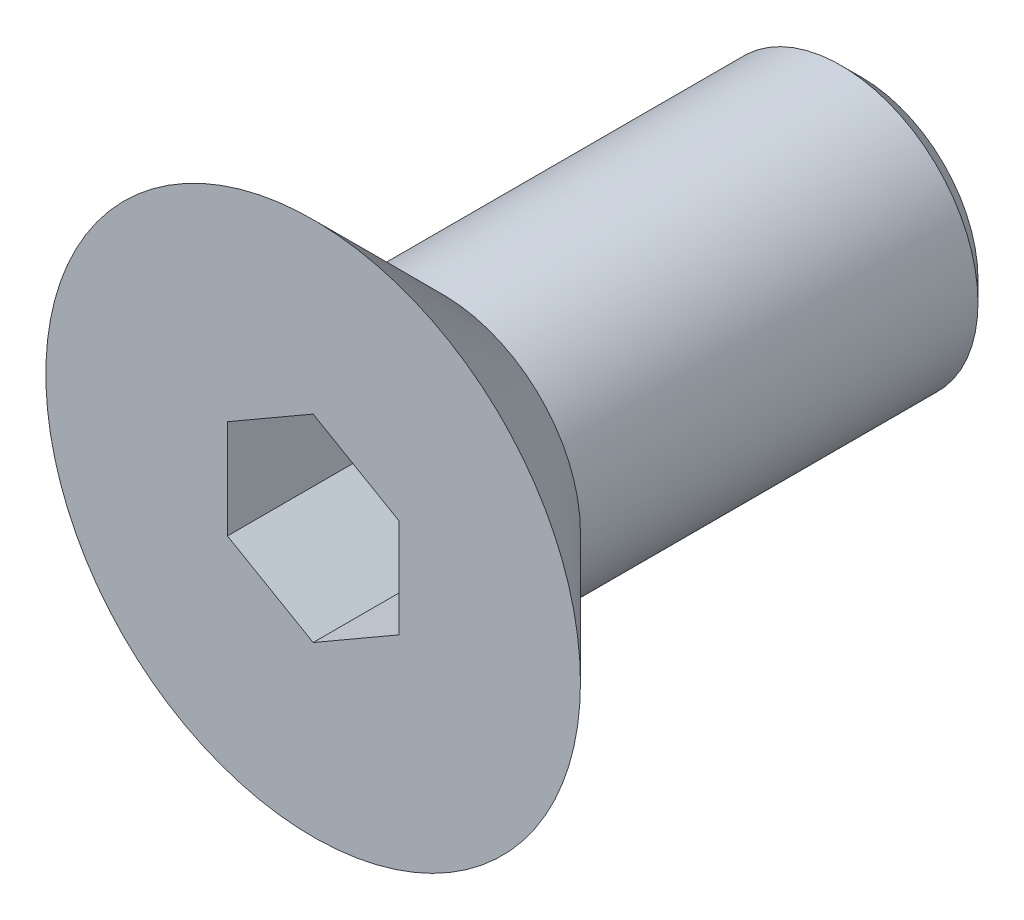
SolidWorks part; units mm, degrees
ref_plane "Front Plane" through (0, 0, 0) normal (0, 0, 1) x (1, 0, 0)
ref_plane "Top Plane" through (0, 0, 0) normal (0, 1, 0) x (1, 0, 0)
ref_plane "Right Plane" through (0, 0, 0) normal (1, 0, 0) x (0, 0, -1)
sketch "Sketch1" plane through (0, 0, 0) normal (0, 0, 1) x (1, 0, 0)
  circle A0 centre (0, 0) radius 4
  dimension "D1" = 8
extrude "Boss-Extrude1" add sketch "Sketch1" along normal blind 2.3
sketch "Sketch2" plane through (0, 0, 0) normal (0, 0, -1) x (-1, 0, 0)
  circle A0 centre (0, 0) radius 2
  dimension "D1" = 4
extrude "Boss-Extrude2" add sketch "Sketch2" along normal blind 5.7
chamfer "Chamfer1" distance 0.3 angle 45 1 edges at (-2, 0, -5.7)
sketch "Sketch3" plane through (0, 0, 2.3) normal (0, 0, 1) x (1, 0, 0)
  line L1 (0, 1.4434) -> (-1.25, 0.7217)
  line L2 (-1.25, 0.7217) -> (-1.25, -0.7217)
  line L3 (-1.25, -0.7217) -> (0, -1.4434)
  line L4 (0, -1.4434) -> (1.25, -0.7217)
  line L5 (1.25, -0.7217) -> (1.25, 0.7217)
  line L6 (1.25, 0.7217) -> (0, 1.4434)
  circle A0 centre (0, 0) radius 1.25 construction
  dimension "D1" = 2.5
extrude "Cut-Extrude1" cut sketch "Sketch3" against normal blind 2
chamfer "Chamfer2" distance 2.4 angle 45 1 edges at (4, 0, 0)
